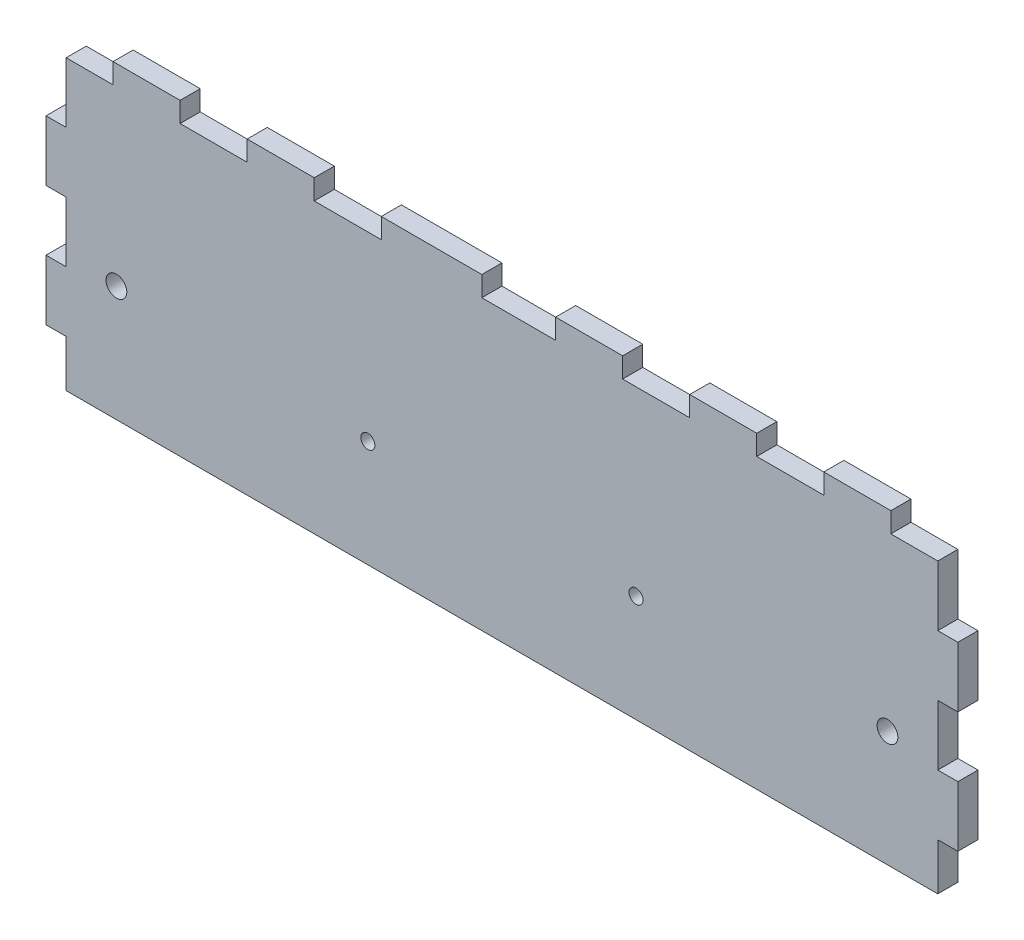
SolidWorks part; units mm, degrees
ref_plane "Front Plane" through (0, 0, 0) normal (0, 0, 1) x (1, 0, 0)
ref_plane "Top Plane" through (0, 0, 0) normal (0, 1, 0) x (1, 0, 0)
ref_plane "Right Plane" through (0, 0, 0) normal (1, 0, 0) x (0, 0, -1)
sketch "Sketch1" plane through (0, 0, 0) normal (0, 0, 1) x (1, 0, 0)
  line L4 (-136, 0) -> (0, 0)
  line L5 (0, 0) -> (0, 46)
  line L6 (0, 46) -> (-136, 46)
  line L7 (-136, 46) -> (-136, 0)
  line L8 (-136, 0) -> (0, 0)
  line L9 (0, 0) -> (0, 46)
  line L10 (0, 46) -> (-136, 46)
  line L11 (-136, 46) -> (-136, 0)
  circle A0 centre (-88, 15.95) radius 1.05 construction
  circle A1 centre (-125.5, 17.25) radius 1.55 construction
  circle A2 centre (-48, 15.95) radius 1.05 construction
  circle A3 centre (-10.5, 17.25) radius 1.55 construction
  circle A4 centre (-88, 15.95) radius 1.05
  circle A5 centre (-125.5, 17.25) radius 1.55
  circle A6 centre (-48, 15.95) radius 1.05
  circle A7 centre (-10.5, 17.25) radius 1.55
  dimension "D1" = 0
extrude "Boss-Extrude1" add sketch "Sketch1" along normal blind 3
sketch "Sketch2" plane through (0, 0, 3) normal (0, 0, 1) x (1, 0, 0)
  line L0 (-133, 43) -> (-133, 34) construction
  line L1 (-133, 34) -> (-136, 34) construction
  line L2 (-136, 34) -> (-136, 43) construction
  line L3 (-136, 43) -> (-133, 43) construction
  line L4 (-133, 25) -> (-133, 16) construction
  line L5 (-133, 16) -> (-136, 16) construction
  line L6 (-136, 16) -> (-136, 25) construction
  line L7 (-136, 25) -> (-133, 25) construction
  line L8 (-136, 0) -> (-136, 7) construction
  line L9 (-136, 7) -> (-133, 7) construction
  line L10 (-133, 7) -> (-133, 0) construction
  line L11 (-133, 0) -> (-136, 0) construction
  line L12 (-136, 46) -> (-126, 46) construction
  line L13 (-126, 46) -> (-126, 43) construction
  line L14 (-126, 43) -> (-136, 43) construction
  line L15 (-136, 43) -> (-136, 46) construction
  line L16 (-116, 46) -> (-106, 46) construction
  line L17 (-106, 46) -> (-106, 43) construction
  line L18 (-106, 43) -> (-116, 43) construction
  line L19 (-116, 43) -> (-116, 46) construction
  line L20 (-86, 43) -> (-96, 43) construction
  line L21 (-96, 43) -> (-96, 46) construction
  line L22 (-96, 46) -> (-86, 46) construction
  line L23 (-86, 46) -> (-86, 43) construction
  line L24 (-60, 43) -> (-71, 43) construction
  line L25 (-71, 43) -> (-71, 46) construction
  line L26 (-71, 46) -> (-60, 46) construction
  line L27 (-60, 46) -> (-60, 43) construction
  line L28 (-40, 43) -> (-50, 43) construction
  line L29 (-50, 43) -> (-50, 46) construction
  line L30 (-50, 46) -> (-40, 46) construction
  line L31 (-40, 46) -> (-40, 43) construction
  line L32 (-20, 43) -> (-30, 43) construction
  line L33 (-30, 43) -> (-30, 46) construction
  line L34 (-30, 46) -> (-20, 46) construction
  line L35 (-20, 46) -> (-20, 43) construction
  line L36 (0, 43) -> (-10, 43) construction
  line L37 (-10, 43) -> (-10, 46) construction
  line L38 (-10, 46) -> (0, 46) construction
  line L39 (0, 46) -> (0, 43) construction
  line L40 (0, 43) -> (0, 34) construction
  line L41 (0, 34) -> (-3, 34) construction
  line L42 (-3, 34) -> (-3, 43) construction
  line L43 (-3, 43) -> (0, 43) construction
  line L44 (0, 25) -> (0, 16) construction
  line L45 (0, 16) -> (-3, 16) construction
  line L46 (-3, 16) -> (-3, 25) construction
  line L47 (-3, 25) -> (0, 25) construction
  line L48 (-3, 0) -> (-3, 7) construction
  line L49 (-3, 7) -> (0, 7) construction
  line L50 (0, 7) -> (0, 0) construction
  line L51 (0, 0) -> (-3, 0) construction
  line L52 (-133, 43) -> (-133, 34)
  line L53 (-133, 34) -> (-136, 34)
  line L54 (-136, 34) -> (-136, 43)
  line L55 (-136, 43) -> (-133, 43)
  line L56 (-133, 25) -> (-133, 16)
  line L57 (-133, 16) -> (-136, 16)
  line L58 (-136, 16) -> (-136, 25)
  line L59 (-136, 25) -> (-133, 25)
  line L60 (-136, 0) -> (-136, 7)
  line L61 (-136, 7) -> (-133, 7)
  line L62 (-133, 7) -> (-133, 0)
  line L63 (-133, 0) -> (-136, 0)
  line L64 (-136, 46) -> (-126, 46)
  line L65 (-126, 46) -> (-126, 43)
  line L66 (-126, 43) -> (-136, 43)
  line L67 (-136, 43) -> (-136, 46)
  line L68 (-116, 46) -> (-106, 46)
  line L69 (-106, 46) -> (-106, 43)
  line L70 (-106, 43) -> (-116, 43)
  line L71 (-116, 43) -> (-116, 46)
  line L72 (-86, 43) -> (-96, 43)
  line L73 (-96, 43) -> (-96, 46)
  line L74 (-96, 46) -> (-86, 46)
  line L75 (-86, 46) -> (-86, 43)
  line L76 (-60, 43) -> (-71, 43)
  line L77 (-71, 43) -> (-71, 46)
  line L78 (-71, 46) -> (-60, 46)
  line L79 (-60, 46) -> (-60, 43)
  line L80 (-40, 43) -> (-50, 43)
  line L81 (-50, 43) -> (-50, 46)
  line L82 (-50, 46) -> (-40, 46)
  line L83 (-40, 46) -> (-40, 43)
  line L84 (-20, 43) -> (-30, 43)
  line L85 (-30, 43) -> (-30, 46)
  line L86 (-30, 46) -> (-20, 46)
  line L87 (-20, 46) -> (-20, 43)
  line L88 (0, 43) -> (-10, 43)
  line L89 (-10, 43) -> (-10, 46)
  line L90 (-10, 46) -> (0, 46)
  line L91 (0, 46) -> (0, 43)
  line L92 (0, 43) -> (0, 34)
  line L93 (0, 34) -> (-3, 34)
  line L94 (-3, 34) -> (-3, 43)
  line L95 (-3, 43) -> (0, 43)
  line L96 (0, 25) -> (0, 16)
  line L97 (0, 16) -> (-3, 16)
  line L98 (-3, 16) -> (-3, 25)
  line L99 (-3, 25) -> (0, 25)
  line L100 (-3, 0) -> (-3, 7)
  line L101 (-3, 7) -> (0, 7)
  line L102 (0, 7) -> (0, 0)
  line L103 (0, 0) -> (-3, 0)
  line M3 (-136, 46) -> (-136, 0)
  line M4 (-136, 0) -> (0, 0)
  line M5 (0, 0) -> (0, 46)
  line M6 (0, 46) -> (-136, 46)
extrude "Cut-Extrude1" cut sketch "Sketch2" against normal up to next contours L79 L77 L76 M6 | L75 L73 L72 M6 | L71 L70 L69 M6 | L66 L65 L55 M6 M3 | L55 L53 L52 M3 | L59 L57 L56 M3 | L62 L61 M3 M4 | L101 L100 M4 M5 | L99 L98 L97 M5 | L94 L93 L88 M5 | L89 L88 M5 M6 | L87 L85 L84 M6 | L83 L81 L80 M6 region at (-134.5, 38.5, 3) region at (-131, 44.5, 3) region at (-134.5, 20.5, 3) region at (-111, 44.5, 3) region at (-134.5, 3.5, 3) region at (-91, 44.5, 3) region at (-65.5, 44.5, 3) region at (-1.5, 3.5, 3) region at (-45, 44.5, 3) region at (-1.5, 20.5, 3) region at (-25, 44.5, 3) region at (-1.5, 38.5, 3) region at (-5, 44.5, 3)
